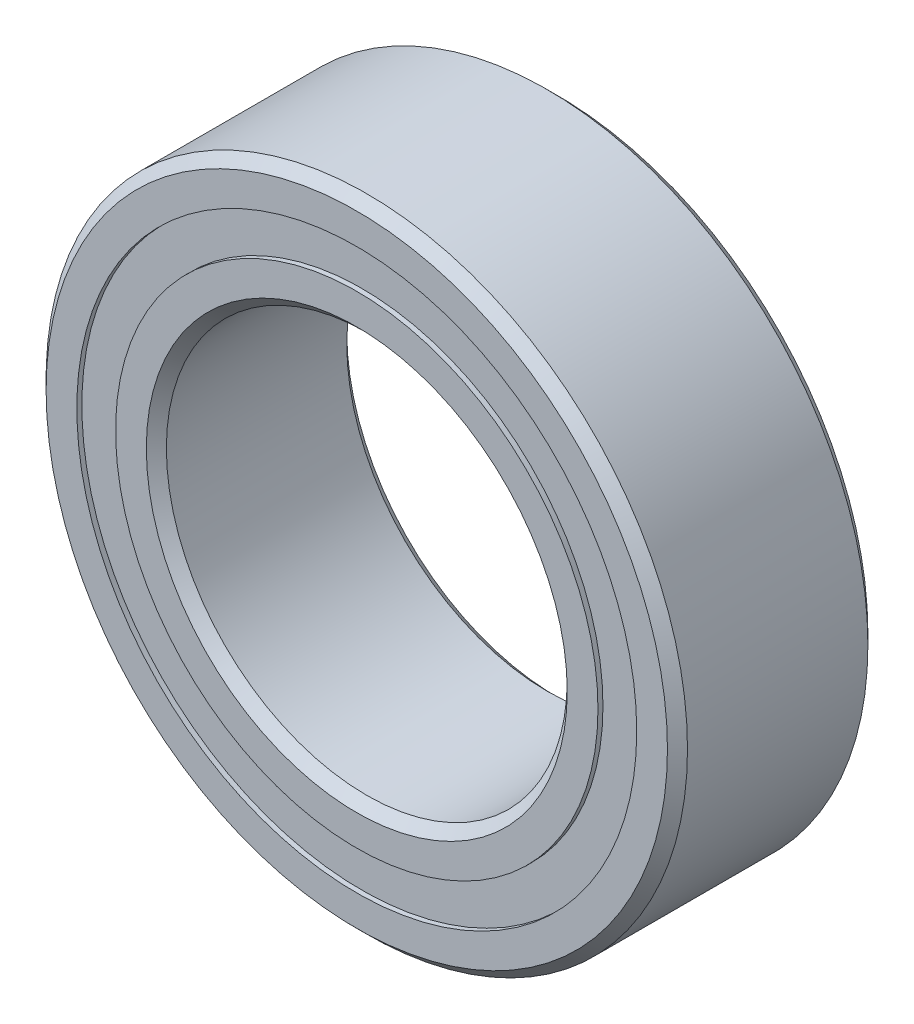
SolidWorks part; units mm, degrees
ref_plane "Front Plane" through (0, 0, 0) normal (0, 0, 1) x (1, 0, 0)
ref_plane "Top Plane" through (0, 0, 0) normal (0, 1, 0) x (1, 0, 0)
ref_plane "Right Plane" through (0, 0, 0) normal (1, 0, 0) x (0, 0, -1)
sketch "Sketch1" plane through (0, 0, 0) normal (1, 0, 0) x (0, 0, -1)
  line L0 (-1.25, 0) -> (1.25, 0) construction
  line L1 (0, 4) -> (0, -4) construction
  line L2 (1.125, 4) -> (-1.125, 4)
  line L3 (-1.125, 4) -> (-1.25, 3.875)
  line L4 (-1.25, 3.875) -> (-1.25, 3.4918)
  line L5 (-1.25, 3.4918) -> (-0.5556, 3.4918)
  line L6 (1.25, 3.4918) -> (0.5556, 3.4918)
  line L7 (1.25, 3.875) -> (1.25, 3.4918)
  line L8 (1.125, 4) -> (1.25, 3.875)
  line L9 (0, 4) -> (0, 3.25) construction
  line L10 (0, 3.25) -> (0, 2.5) construction
  arc A0 (-0.5556, 3.4918) -> (0.5556, 3.4918) centre (0, 3.25) cw
  point P14 (0, 2.5)
  dimension "Width" = 2.5
  dimension "OD" = 8
  dimension "D1" = 45
  dimension "D2" = 0.125
  dimension "Shaft Dia" = 5
  dimension "D3" = 1.1111
  dimension "D4" = 0.2418
revolve "Revolve1" add sketch "Sketch1" angle 360 about L0
sketch "Sketch3" plane through (0, 0, 0) normal (1, 0, 0) x (0, 0, -1)
  line L0 (-1.25, 3.0082) -> (-0.5556, 3.0082)
  line L1 (0, 4) -> (0, -4) construction
  line L2 (-1.25, 3.875) -> (-1.25, 3.4918) construction
  line L3 (-1.25, 3.0082) -> (-1.25, 2.625)
  line L4 (-1.125, 4) -> (-1.25, 3.875) construction
  line L5 (-1.25, 2.625) -> (-1.125, 2.5)
  line L6 (-1.125, 2.5) -> (1.125, 2.5)
  line L7 (1.125, 4) -> (1.125, -4) construction
  line L8 (1.125, 2.5) -> (1.25, 2.625)
  line L9 (1.25, -3.875) -> (1.25, 3.875) construction
  line L10 (1.25, 2.625) -> (1.25, 3.0082)
  line L11 (1.25, 3.0082) -> (0.5556, 3.0082)
  line L13 (1.125, 4) -> (1.25, 3.875) construction
  arc A0 (0.5556, 3.4918) -> (-0.5556, 3.4918) centre (0, 3.25) ccw construction
  arc A1 (0.5556, 3.0082) -> (-0.5556, 3.0082) centre (0, 3.25) cw
revolve "Revolve3" add sketch "Sketch3" angle 360 about L0
sketch "Sketch4" plane through (0, 0, 0) normal (1, 0, 0) x (0, 0, -1)
  line L0 (-0.6059, 3.25) -> (0.6059, 3.25)
  arc A2 (-0.6059, 3.25) -> (0.6059, 3.25) centre (0, 3.25) cw
  arc A3 (0.5556, 3.4918) -> (-0.5556, 3.4918) centre (0, 3.25) ccw construction
revolve "Revolve4" add sketch "Sketch4" angle 360 about L0
ref_axis "Axis1" through (0, 0, -1.25) along (0, 0, 1)
pattern_circular "CirPattern1" count 12 every 30 about axis through (0, 0, -1.25) along (0, 0, 1) of bodies 104
sketch "Sketch5" plane through (0, 0, 0) normal (1, 0, 0) x (0, 0, -1)
  line L0 (-1.25, 3.4918) -> (-0.5556, 3.4918) construction
  line L1 (-1.1875, 3.4918) -> (-0.6059, 3.4918)
  line L2 (-1.1875, 3.4918) -> (-1.1875, 3.0082)
  line L3 (-1.1875, 3.0082) -> (-0.6059, 3.0082)
  line L4 (-0.6059, 3.4918) -> (-0.6059, 3.0082)
  line L5 (-1.25, 3.0082) -> (-0.5556, 3.0082) construction
  line L6 (1.25, 3.4918) -> (0.5556, 3.4918) construction
  line L7 (1.1875, 3.4918) -> (0.6059, 3.4918)
  line L8 (1.1875, 3.4918) -> (1.1875, 3.0082)
  line L9 (1.1875, 3.0082) -> (0.6059, 3.0082)
  line L10 (0.6059, 3.4918) -> (0.6059, 3.0082)
  line L11 (1.25, 3.0082) -> (0.5556, 3.0082) construction
  line L12 (-1.125, 4) -> (-1.25, 3.875) construction
  point P18 (-1.1875, 3.9375)
revolve "Revolve5" add sketch "Sketch5" angle 360 about L0
sketch "Sketch6" plane through (0, 0, 0) normal (1, 0, 0) x (0, 0, -1)
  line L0 (1.25, 0) -> (-1.25, 0) construction
  line L1 (1.25, 3.4918) -> (0.15, 3.4918)
  line L2 (1.25, 3.4918) -> (1.25, 9.5)
  line L3 (1.25, 9.5) -> (0.15, 9.5)
  line L4 (0.15, 3.4918) -> (0.15, 9.5)
  dimension "Th" = 1.1
  dimension "Flange OD" = 19
revolve "Revolve6" [suppressed] add sketch "Sketch6" angle 360 about L0
equation "\"D2@Sketch1\" = \"Width@Sketch1\"*.05"
equation "\"D3@Sketch1\" = \"Width@Sketch1\"/2.25"
equation "\"D4@Sketch1\" = (((\"OD@Sketch1\"-\"Width@Sketch1\")/2)/3.25)/3.5"
equation "\"D2@CirPattern1\" = 360/\"Balls@CirPattern1\""
